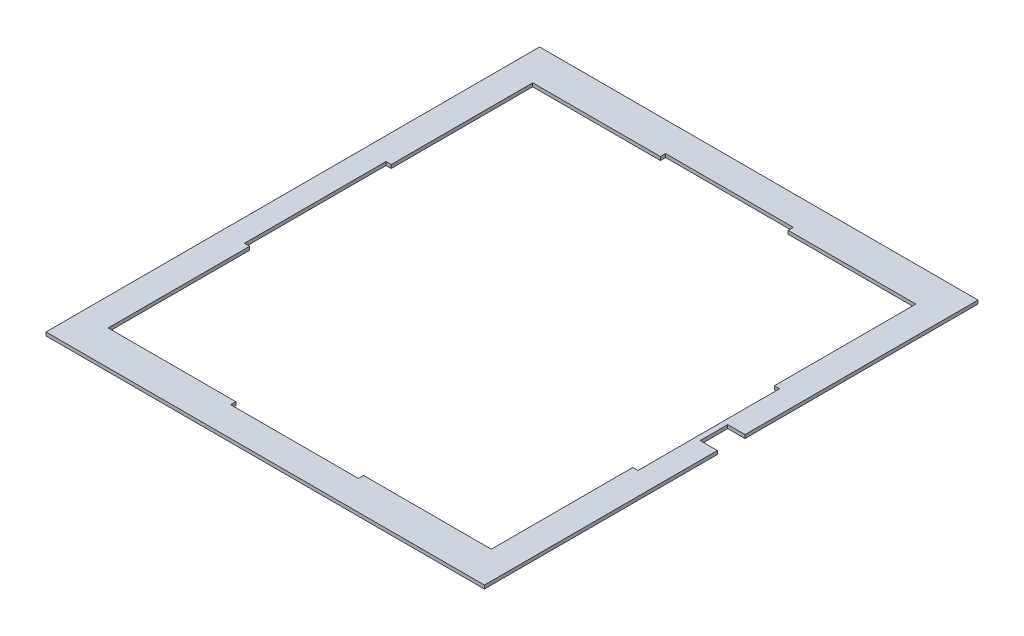
SolidWorks part; units mm, degrees
ref_plane "Front Plane" through (0, 0, 0) normal (0, 0, 1) x (1, 0, 0)
ref_plane "Top Plane" through (0, 0, 0) normal (0, 1, 0) x (1, 0, 0)
ref_plane "Right Plane" through (0, 0, 0) normal (1, 0, 0) x (0, 0, -1)
sketch "Sketch1" plane through (0, 0, 0) normal (0, 1, 0) x (1, 0, 0)
  line L0 (37, 123) -> (111, 123)
  line L1 (-111, -123) -> (-37, -123)
  line L2 (-111, -123) -> (-111, -41)
  line L3 (-111, 123) -> (-37, 123)
  line L4 (111, -123) -> (111, -41)
  line L5 (-111, -123) -> (111, 123) construction
  line L6 (-111, 123) -> (111, -123) construction
  line L7 (-127, -143) -> (127, -143)
  line L8 (-127, -143) -> (-127, 143)
  line L9 (-127, 143) -> (127, 143)
  line L10 (127, -143) -> (127, -8)
  line L11 (-127, -143) -> (127, 143) construction
  line L12 (-127, 143) -> (127, -143) construction
  line L13 (111, 41) -> (111, 123)
  line L14 (37, 123) -> (37, 126)
  line L15 (37, 126) -> (-37, 126)
  line L16 (-37, 123) -> (-37, 126)
  line L17 (-111, 41) -> (-111, 123)
  line L18 (37, -123) -> (37, -126)
  line L19 (37, -126) -> (-37, -126)
  line L20 (-37, -123) -> (-37, -126)
  line L21 (-111, -41) -> (-114, -41)
  line L22 (127, 8) -> (127, 143)
  line L23 (-111, 41) -> (-114, 41)
  line L24 (-114, -41) -> (-114, 41)
  line L25 (111, -41) -> (114, -41)
  line L26 (37, -123) -> (111, -123)
  line L27 (111, 41) -> (114, 41)
  line L28 (114, -41) -> (114, 41)
  line L29 (127, -8) -> (117, -8)
  line L31 (127, 8) -> (117, 8)
  line L32 (117, -8) -> (117, 8)
  point P0 (0, 0)
  point P5 (0, 0)
  dimension "D1" = 222
  dimension "D2" = 246
  dimension "D3" = 20
  dimension "D4" = 16
  dimension "D5" = 3
  dimension "D6" = 10
  dimension "D7" = 16
extrude "Boss-Extrude1" add sketch "Sketch1" along normal blind 2
equation "\"Resolution Projector X\"= 1920"
equation "\"Resolution Projector Y\"= 1080"
equation "\"Resolution Build\"= 0.1"
equation "\"Size Build Volume X\"= \"Resolution Projector X\" * \"Resolution Build\""
equation "\"Size Build Volume Y\"= 2 * \"Resolution Projector Y\" * \"Resolution Build\""
equation "\"Size Build Volume Z\"= \"Size Build Volume Y\""
equation "\"Thick\"= 0.125in"
equation "\"Size Enclosure Internal X\"= 350mm"
equation "\"Size Enclosure Internal Y\"= \"Size Enclosure Internal X\""
equation "\"Size Enclosure Internal Z\"= \"Size Enclosure Internal X\""
equation "\"Size Enclosure External Z\"= 1000mm"
equation "\"Diameter Screw\"= 3mm"
equation "\"Diameter Nut\"= 5.5mm"
equation "\"Thick Nut\"= 2.5mm"
equation "\"Length Screw\"= 12mm"
equation "\"D1@Sketch1\"=\"Size Build Volume X\"+30"
equation "\"D2@Sketch1\"=\"Size Build Volume Y\"+30"
equation "\"D4@Sketch1\"=16"
